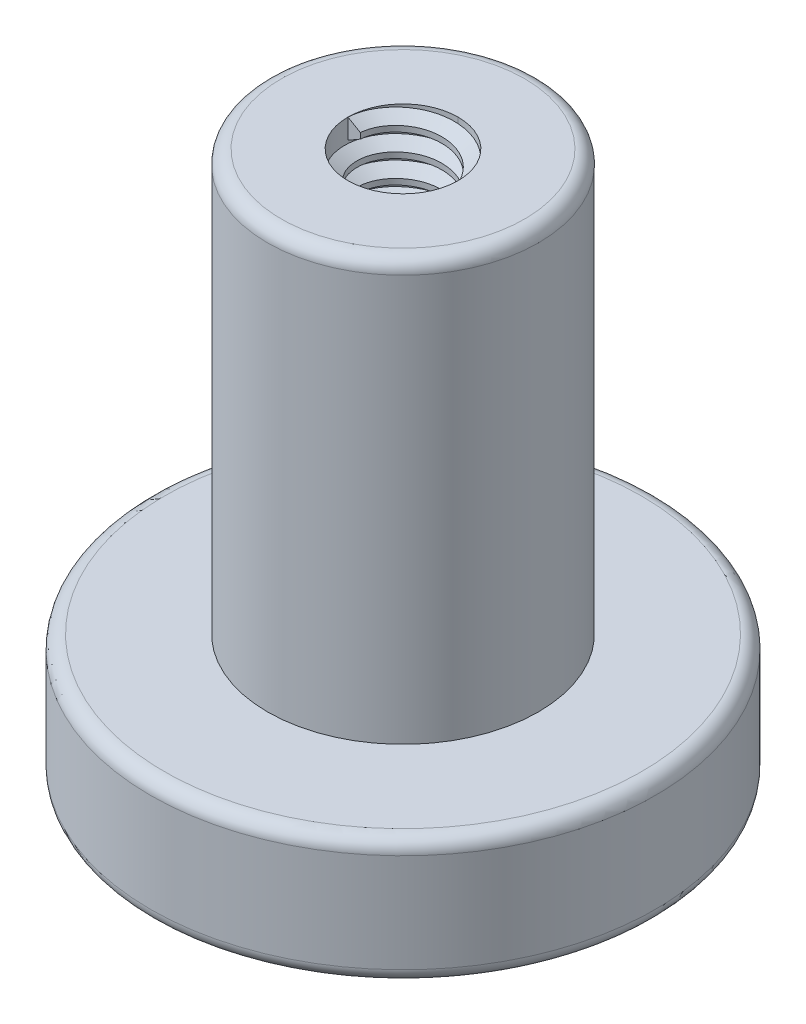
SolidWorks part; units mm, degrees
ref_plane "Front Plane" through (0, 0, 0) normal (0, 0, 1) x (1, 0, 0)
ref_plane "Top Plane" through (0, 0, 0) normal (0, 1, 0) x (1, 0, 0)
ref_plane "Right Plane" through (0, 0, 0) normal (1, 0, 0) x (0, 0, -1)
sketch "Sketch1" plane through (0, 0, 0) normal (1, 0, 0) x (0, 0, -1)
  line L0 (0, 0) -> (0, 13.5588) construction
  line L3 (-2.95, 11.3) -> (-2.95, 2.15)
  line L4 (-2.95, 2.15) -> (-5.5, 2.15)
  line L5 (-5.5, 2.15) -> (-5.5, -0.6)
  line L6 (-5.5, -0.6) -> (-4.3, -0.6)
  line L7 (-4.3, -0.6) -> (-4.3, 0)
  line L8 (-4.3, 0) -> (-2.5, 0)
  line L9 (-2.5, 0) -> (-2.5, 1.2)
  line L10 (-2.5, 1.2) -> (-2.1, 1.2)
  line L11 (-2.1, 1.2) -> (-2.1, 7.5)
  line L13 (-1.2, 11.3) -> (-1.2, 7.5)
  line L14 (-1.2, 7.5) -> (-2.1, 7.5)
  line L15 (-2.95, 11.3) -> (-1.2, 11.3)
  point P4 (-2.3, 0.5753)
  dimension "D1" = 2.95
  dimension "D2" = 5.5
  dimension "D3" = 0.6
  dimension "D4" = 3
  dimension "D5" = 2.1
  dimension "D6" = 1.75
  dimension "D7" = 3.8
  dimension "D8" = 2.75
  dimension "D9" = 1.2
  dimension "D10" = 11.9
  dimension "D11" = 1.2
revolve "Revolve1" add sketch "Sketch1" angle 360 about L0
fillet "Fillet1" radius 0.3 3 edges at (0, 11.3, -2.95) (0, -0.6, -5.5) (0, 2.15, -5.5)
chamfer "Chamfer1" distance 1 angle 45 1 edges at (0, 1.2, -2.1)
fillet "Fillet2" radius 0.1 3 edges at (0, -0.6, -4.3) (0, 0, -4.3) (0, 0, -2.5)
thread "Thread1" pitch 0.5 method extrude profile "Thread Profile2" start angle 0, offset 0, length 3, pitch 0.5, diameter 2.4
ref_plane "Plane2" through (-1.2, 11.3, 0) normal (0, 0, 1) x (-1, 0, 0)
sketch "Thread Profile2" plane through (-1.2, 11.3, 0) normal (0, 0, 1) x (-1, 0, 0)
  line L0 (0, 0) -> (0, 0.5) construction
  line L11 (0, 0) -> (0, 0.4375)
  line L12 (0, 0.4375) -> (-0.2706, 0.2812)
  line L13 (-0.2706, 0.2812) -> (-0.2706, 0.1562)
  line L15 (-0.2706, 0.1562) -> (0, 0)
  line L17 (-0.2706, 0.2187) -> (0, 0.2187) construction
  point P2 (0, 0)
  dimension "Pitch" = 0.5
  dimension "Profile_Angle" = 60
  dimension "Profile_Land" = 0.125
  dimension "Profile_Height" = 0.2706
